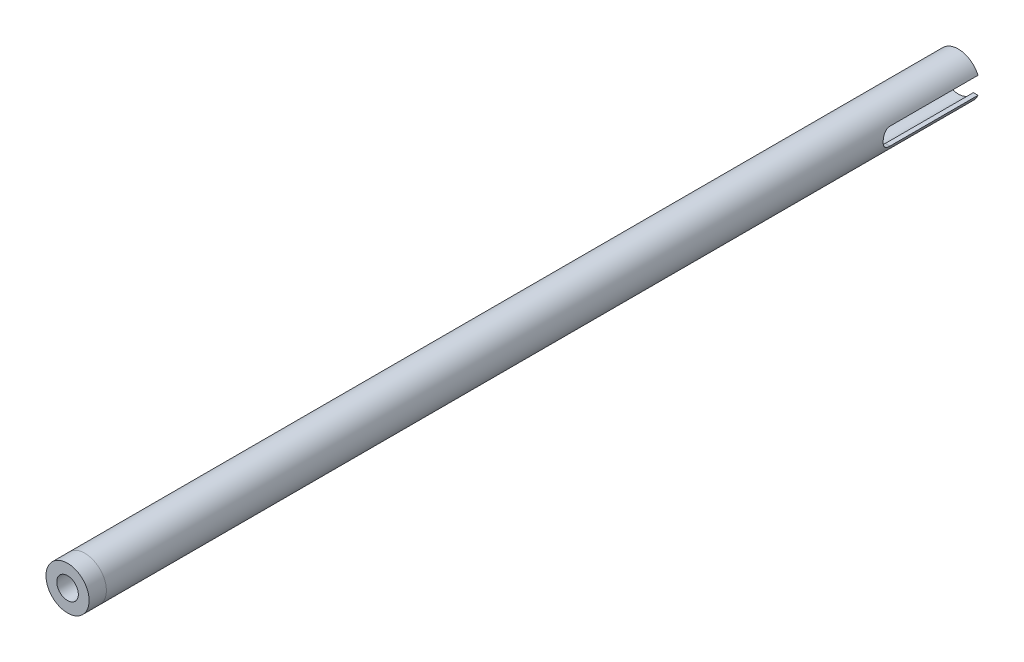
SolidWorks part; units mm, degrees
material "AISI 4130 Steel, annealed at 865C"
ref_plane "Front Plane" through (0, 0, 0) normal (0, 0, 1) x (1, 0, 0)
ref_plane "Top Plane" through (0, 0, 0) normal (0, 1, 0) x (1, 0, 0)
ref_plane "Right Plane" through (0, 0, 0) normal (1, 0, 0) x (0, 0, -1)
sketch "Axis" plane through (0, 0, 0) normal (0, 1, 0) x (1, 0, 0)
  line L0 (0, 0) -> (0, 327.5709) construction
  line L1 (0, 0) -> (0, -28.575) construction
  line L2 (0, 327.5709) -> (-7.9375, 327.5709) construction
  line L3 (0, 355.931) -> (-26.4723, 261.3474) construction
  dimension "D1" = 28.575
  dimension "D2" = 7.9375
sketch "Sketch1" plane through (0, 0, 0) normal (0, 0, 1) x (1, 0, 0)
  line L0 (-7.9375, 0) -> (7.9375, 0) construction
  line L1 (-7.2748, 3.175) -> (7.2748, 3.175)
  line L2 (-7.2748, -3.175) -> (7.2748, -3.175)
  circle A0 centre (0, 0) radius 7.9375
  circle A1 centre (0, 0) radius 6.4135
  circle A2 centre (0, 0) radius 3.9688
  dimension "D1" = 15.875
  dimension "D3" = 7.9375
  dimension "D2" = 1.524
  dimension "D4" = 6.35
extrude "Threaded insert 1-1" add sketch "Sketch1" against normal blind 6.35 contours A2 L1 A1 | A1 L1 A0 | A2 L0 A1 L1 | A1 L0 A0 L1 | L0 A1 L2 A0 | L0 A2 L2 A1 | A2 L2 A1 | A1 L2 A0 | L0 A1 L2 A2 | L0 A0 L2 A1 | A0 L0 A1 L1 | A1 L0 A2 L1 region at (4.7887, 1.6543, 0) region at (4.7887, -1.6543, 0) region at (6.9234, 1.6163, 0) region at (6.9234, -1.6163, 0) region at (-4.7887, -1.6543, 0) region at (-4.7887, 1.6543, 0) region at (0, 4.6159, 0) region at (0, -4.6159, 0) region at (0, 6.5666, 0) region at (6.4237, -3.3281, 0) region at (-6.9234, -1.6163, 0) region at (-6.9234, 1.6163, 0)
extrude "Threaded insert 1-2" add sketch "Sketch1<3>" against normal blind 9.525 from surface contours A2 L1 A1 | A2 L0 A1 L1 | L0 A2 L2 A1 | A2 L2 A1 | L0 A1 L2 A2 | A1 L0 A2 L1 region at (4.7887, 1.6543, 0) region at (4.7887, -1.6543, 0) region at (-4.7887, -1.6543, 0) region at (-4.7887, 1.6543, 0) region at (0, 4.6159, 0) region at (0, -4.6159, 0) starting at face at (7.9375, 0, -6.35)
sketch "Sketch1<3>" plane through (0, 0, 0) normal (0, 0, 1) x (1, 0, 0) same geometry as "Sketch1"
extrude "A-arm tube" add sketch "Sketch1<4>" against normal up to vertex (327.5709 mm away) from surface separate body contours A1 L1 A0 | A1 L0 A0 L1 | L0 A1 L2 A0 | A1 L2 A0 | L0 A0 L2 A1 | A0 L0 A1 L1 region at (6.9234, 1.6163, 0) region at (6.9234, -1.6163, 0) region at (0, 6.5666, 0) region at (6.4237, -3.3281, 0) region at (-6.9234, -1.6163, 0) region at (-6.9234, 1.6163, 0) up to point (0, 0, -327.5709) starting at face at (6.4135, 0, -6.35)
sketch "Sketch1<4>" plane through (0, 0, 0) normal (0, 0, 1) x (1, 0, 0) same geometry as "Sketch1"
extrude "Apex slot" cut sketch "Sketch1<5>" along normal blind 35.56 from surface contours A0 L0 A1 L1 | L0 A0 L2 A1 | A1 L0 A0 L1 | L0 A1 L2 A0 region at (6.9234, 1.6163, 0) region at (6.9234, -1.6163, 0) region at (-6.9234, -1.6163, 0) region at (-6.9234, 1.6163, 0) starting at face at (6.4135, 0, -327.5709)
sketch "Sketch1<5>" plane through (0, 0, 0) normal (0, 0, 1) x (1, 0, 0) same geometry as "Sketch1"
fillet "Fillet1" radius 3.175 4 edges at (-6.4237, 3.175, -292.0109) (-6.4237, -3.175, -292.0109) (6.4237, -3.175, -292.0109) (6.4237, 3.175, -292.0109)
equation "\"tube diameter\"= 5 / 8"
equation "\"tube thickness\"= .06"
equation "\"apex thickness\"= .25"
equation "\"tube slot\"= 1.4"
equation "\"D1@Sketch1\"=\"tube diameter\""
equation "\"D2@Sketch1\"=\"tube thickness\""
equation "\"threaded insert hole\"= .3125"
equation "\"D3@Sketch1\"=\"threaded insert hole\""
equation "\"D4@Sketch1\"=\"apex thickness\""
equation "\"D1@Apex slot\" = \"tube slot\""
equation "\"D1@Fillet1\"=\"apex thickness\"/2"
